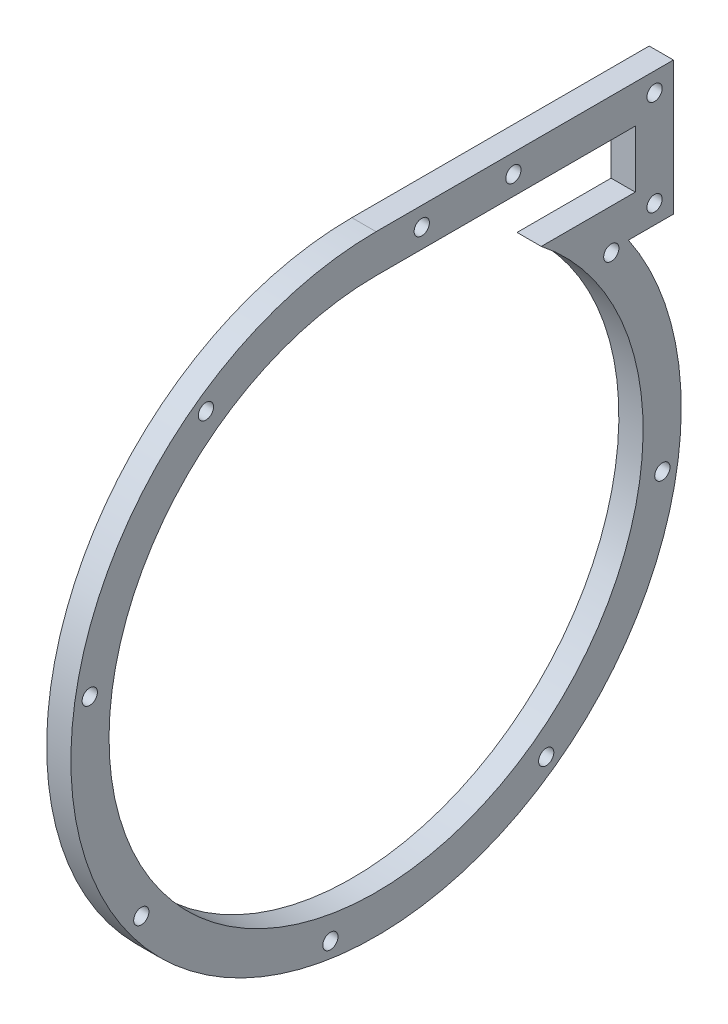
SolidWorks part; units mm, degrees
ref_plane "Front Plane" through (0, 0, 0) normal (0, 0, 1) x (1, 0, 0)
ref_plane "Top Plane" through (0, 0, 0) normal (0, 1, 0) x (1, 0, 0)
ref_plane "Right Plane" through (0, 0, 0) normal (1, 0, 0) x (0, 0, -1)
sketch "Sketch1" plane through (0, 0, 0) normal (1, 0, 0) x (0, 0, -1)
  line L0 (0, 80) -> (77.95, 80)
  line L1 (77.95, 80) -> (77.95, 45)
  line L2 (77.95, 45) -> (66.1438, 45)
  line L3 (67.95, 55) -> (43.3013, 55)
  line L4 (67.95, 70) -> (67.95, 55)
  line L5 (0, 70) -> (67.95, 70)
  arc A0 (0, 80) -> (66.1438, 45) centre (0, 0) ccw
  arc A1 (0, 70) -> (43.3013, 55) centre (0, 0) ccw
  dimension "D1" = 70
  dimension "D3" = 15
  dimension "D2" = 10
extrude "Boss-Extrude1" add sketch "Sketch1" along normal blind 6.35
sketch "Sketch2" plane through (6.35, 0, 0) normal (1, 0, 0) x (0, 0, -1)
  circle A0 centre (73, 75.05) radius 2
  circle A1 centre (73, 49.95) radius 2
  circle A2 centre (61.6656, 44.4224) radius 2
  circle A3 centre (75.05, -11.979) radius 2
  circle A4 centre (44.5979, -61.5388) radius 2
  circle A5 centre (-11.979, -75.05) radius 2
  circle A6 centre (-61.5388, -44.5979) radius 2
  circle A7 centre (-75.05, 11.979) radius 2
  circle A8 centre (-44.5979, 61.5388) radius 2
  circle A9 centre (11.979, 75.05) radius 2
  circle A10 centre (36, 75.05) radius 2
  point P0 (73, 75.05)
  point P1 (73, 49.95)
  point P3 (61.6656, 44.4224)
  point P5 (75.05, -11.979)
  point P7 (44.5979, -61.5388)
  point P9 (-11.979, -75.05)
  point P11 (-61.5388, -44.5979)
  point P13 (-75.05, 11.979)
  point P15 (-44.5979, 61.5388)
  point P17 (11.979, 75.05)
  point P19 (36, 75.05)
  dimension "D1" = 4
  dimension "D2" = 4
  dimension "D3" = 4
  dimension "D4" = 4
  dimension "D5" = 4
  dimension "D6" = 4
  dimension "D7" = 4
  dimension "D8" = 4
  dimension "D9" = 4
  dimension "D10" = 4
  dimension "D11" = 4
extrude "Cut-Extrude1" cut sketch "Sketch2" against normal through all
